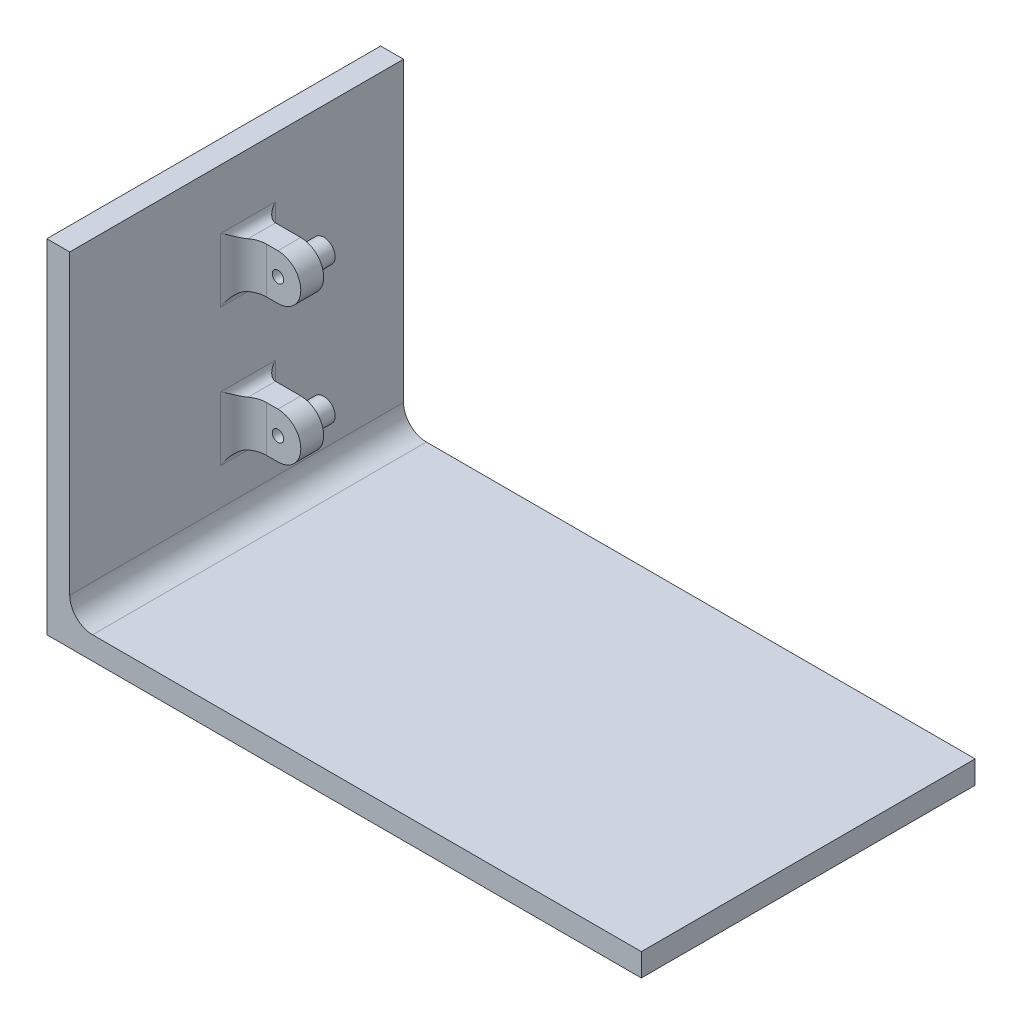
SolidWorks part; units mm, degrees
note: '?' marks a value the reader was unsure of.
material "PET"
ref_plane "Piano frontale" through (0, 0, 0) normal (0, 0, 1) x (1, 0, 0)
ref_plane "Piano superiore" through (0, 0, 0) normal (0, 1, 0) x (1, 0, 0)
ref_plane "Piano destro" through (0, 0, 0) normal (1, 0, 0) x (0, 0, -1)
sketch "Schizzo1" plane through (0, 0, 0) normal (0, 0, 1) x (1, 0, 0)
  line L1 (0, 0) -> (-5, 0)
  line L2 (0, 0) -> (0, 70)
  line L3 (0, 70) -> (-5, 70)
  line L4 (-5, 0) -> (-5, 70)
  dimension "D1" = 70
  dimension "D2" = 5
extrude "Estrusione-Estrusione1" add sketch "Schizzo1" along normal blind 70
sketch "Schizzo2" plane through (0, 0, 70) normal (0, 0, 1) x (1, 0, 0)
  line L0 (0, 15) -> (0, 20)
  line L1 (0, 0) -> (0, 70) construction
  line L2 (0, 45) -> (0, 50)
  line L3 (7.5316, 55) -> (0, 55)
  line L4 (0, 55) -> (0, 45)
  line L5 (0, 45) -> (7.5316, 45)
  line L6 (7.5316, 25) -> (0, 25)
  line L7 (0, 25) -> (0, 15)
  line L8 (0, 15) -> (7.5316, 15)
  arc A0 (7.5316, 45) -> (7.5316, 55) centre (7.5316, 50) ccw
  arc A1 (7.5316, 15) -> (7.5316, 25) centre (7.5316, 20) ccw
  line M1 (0, 0) -> (0, 70)
  dimension "D1" = 10
  dimension "D2" = 10
extrude "Estrusione-Estrusione2" add sketch "Schizzo2" against normal blind 5 from offset 35 contours L5 A0 L3 M1 | L8 A1 L6 M1 offset against normal yes
sketch "Schizzo3" plane through (0, 0, 30) normal (0, 0, -1) x (-1, 0, 0)
  circle A0 centre (-7.5476, 50.0613) radius 2.5
  circle A1 centre (-7.5476, 19.9398) radius 2.5
  dimension "D1" = 5
  dimension "D2" = 5
extrude "Estrusione-Estrusione3" add sketch "Schizzo3" along normal blind 5
sketch "Schizzo4" plane through (0, 0, 0) normal (0, -1, 0) x (1, 0, 0)
  line L1 (-5, 0) -> (125, 0)
  line L2 (-5, 0) -> (-5, 70)
  line L3 (-5, 70) -> (125, 70)
  line L4 (125, 0) -> (125, 70)
extrude "Estrusione-Estrusione4" add sketch "Schizzo4" along normal blind 5
sketch "Schizzo5" plane through (0, 0, 25) normal (0, 0, -1) x (-1, 0, 0)
  circle A0 centre (-7.5476, 50.0613) radius 1.25
  circle A1 centre (-7.5476, 19.9398) radius 1.25
  dimension "D1" = 2.5
extrude "Taglio-Estrusione1" cut sketch "Schizzo5" against normal through all
sketch "Schizzo6" plane through (0, 0, 70) normal (0, 0, 1) x (1, 0, 0)
  line L0 (0, 70) -> (125, 0)
  line L7 (0, 0) -> (0, 70)
  line L8 (0, 70) -> (-5, 70)
  line L9 (-5, 70) -> (-5, -5)
  line L10 (-5, -5) -> (125, -5)
  line L11 (125, -5) -> (125, 0)
  line L12 (125, 0) -> (0, 0)
  line L13 (0, 0) -> (0, 70)
  line L14 (0, 70) -> (-5, 70)
  line L15 (-5, 70) -> (-5, -5)
  line L16 (-5, -5) -> (125, -5)
  line L17 (125, -5) -> (125, 0)
  line L18 (125, 0) -> (0, 0)
  line M7 (0, 0) -> (0, 70)
  line M8 (0, 70) -> (-5, 70)
  line M9 (-5, 70) -> (-5, -5)
  line M10 (-5, -5) -> (125, -5)
  line M11 (125, -5) -> (125, 0)
  line M12 (125, 0) -> (0, 0)
  dimension "D1" = 0
extrude "Estrusione-Estrusione5" add sketch "Schizzo6" along normal blind 3 contours M12 M7 M8 M9 M10 M11 | L0 M7 M12
fillet "Raccordo1" radius 5 3 edges at (0, 0, 35) (0, 35, 70) (62.5, 0, 70)
fillet "Raccordo2" radius 5 2 edges at (0, 20, 35) (0, 50, 35)
fillet "Raccordo3" radius 2 2 edges at (0, 20, 30) (0, 50, 30)
fillet "Raccordo4" radius 2 4 edges at (0, 25, 34) (0, 15, 34) (0, 45, 34) (0, 55, 34)
ref_point "Punto1"
ref_point "Punto2"
ref_axis "Assi1" through (7.5476, 50.0613, 35) along (0, 0, -1)?
ref_axis "Assi2" through (7.5316, 55, 30) along (-1, 0, 0)?
sketch "Schizzo7" plane through (0, 0, 73) normal (0, 0, -1) x (-1, 0, 0)
  line L1 (0, 70) -> (-1.3284, 92.9647)
  line L2 (-1.3284, 92.9647) -> (-187.3478, 164.2529)
  line L3 (-187.3478, 164.2529) -> (-125, 0)
  line L6 (0, 70) -> (0, 5)
  line L7 (-5, 0) -> (-125, 0)
  line L8 (-125, 0) -> (-125, -5)
  line L9 (-125, -5) -> (5, -5)
  line L10 (5, -5) -> (5, 70)
  line L11 (5, 70) -> (0, 70)
  line L12 (0, 70) -> (0, 5)
  line L13 (-5, 0) -> (-125, 0)
  line L14 (-125, 0) -> (-125, -5)
  arc A1 (-5, 0) -> (0, 5) centre (-5, 5) ccw
  arc A2 (-5, 0) -> (0, 5) centre (-5, 5) ccw
  line M16 (-125, 0) -> (0, 70)
  dimension "D1" = 0
extrude "Taglio-Estrusione2" cut sketch "Schizzo7" along normal up to next contours A2 L13 L12 M16
